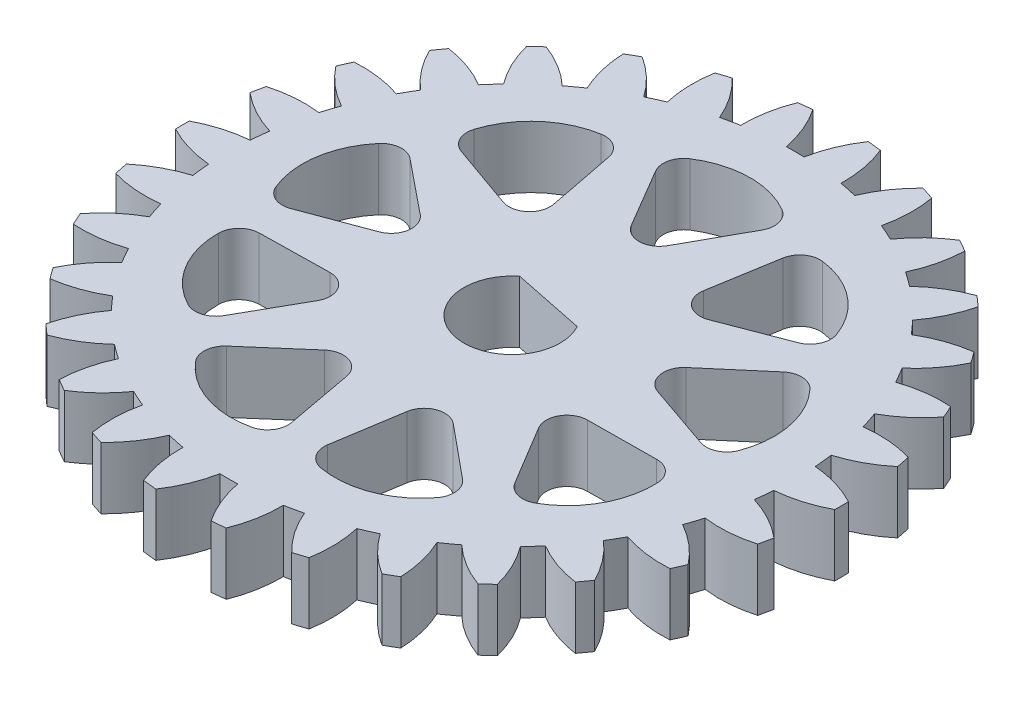
SolidWorks part; units mm, degrees
ref_plane "Front Plane" through (0, 0, 0) normal (0, 0, 1) x (1, 0, 0)
ref_plane "Top Plane" through (0, 0, 0) normal (0, 1, 0) x (1, 0, 0)
ref_plane "Right Plane" through (0, 0, 0) normal (1, 0, 0) x (0, 0, -1)
sketch "Sketch1" plane through (0, 0, 0) normal (0, 1, 0) x (1, 0, 0)
  line L0 (0, 0) -> (0, 30.7861) construction
  line L1 (0, 0) -> (-3.3399, 31.7772) construction
  line L2 (-1.5563, 14.807) -> (-0.7752, 14.8891) construction
  circle A0 centre (0, 0) radius 16
  circle A1 centre (0, 0) radius 13.75 construction
  circle A2 centre (0, 0) radius 14.0954 construction
  circle A3 centre (0, 0) radius 15 construction
  arc A4 (-1.3398, 15.9438) -> (-0.431, 13.7432) centre (-6.3208, 12.5987) cw
  arc A5 (0.431, 13.7432) -> (1.3398, 15.9438) centre (6.3208, 12.5987) cw
  arc A6 (0.431, 13.7432) -> (-0.431, 13.7432) centre (0, 0) ccw
  dimension "addendumDiameter" = 32
  dimension "D1" = 27.5
  dimension "D2" = 28.1908
  dimension "D3" = 30
  dimension "D5" = 6
  dimension "D4" = 6
  dimension "D6" = 0.7854
extrude "Boss-Extrude1" add sketch "Sketch1" along normal blind 3 contours A5 A6 A4 A0 | A6 A5 A0 A4 region at (0, 0, 0.0681) region at (0, 0, -15.0769)
extrude "Cut-Extrude1" cut sketch "Sketch1<3>" along normal through all contours A6 A5 A0 A4 region at (0, 0, -15.0769)
sketch "Sketch1<3>" plane through (0, 0, 0) normal (0, 1, 0) x (1, 0, 0) same geometry as "Sketch1"
pattern_circular "CirPattern1" count 30 over 360 about axis through (0, 3, 0) along (0, -1, 0) of "Cut-Extrude1"
sketch "Sketch2" [suppressed] plane through (0, 0, 0) normal (0, -1, 0) x (1, 0, 0)
  line L0 (16.1415, -4.0765) -> (5.4849, -1.3852)
  line L1 (2.2797, -16.4915) -> (0.7746, -5.6038)
  arc A0 (2.2797, -16.4915) -> (16.1415, -4.0765) centre (0, 0) ccw
  arc A1 (5.4849, -1.3852) -> (0.7746, -5.6038) centre (0, 0) cw
extrude "Cut-Extrude2" [suppressed] cut sketch "Sketch2" against normal through all
fillet "Fillet2" [suppressed] radius 1
pattern_circular "CirPattern2" [suppressed] count 3 over 360 of bodies 105
sketch "Sketch3" [suppressed] plane through (0, 0, 0) normal (0, -1, 0) x (-1, 0, 0)
  line L0 (-1.7523, 1.5) -> (1.7523, 1.5)
  arc A0 (-1.7523, 1.5) -> (1.7523, 1.5) centre (0, 0) ccw
  dimension "D1" = 1.5
extrude "Cut-Extrude3" [suppressed] cut sketch "Sketch3" against normal through all
sketch "Sketch4" [suppressed] plane through (0, 0, 0) normal (0, -1, 0) x (-1, 0, 0)
  line L0 (-1.9585, 1.1467) -> (1.3849, 1.798)
  arc A0 (-1.9585, 1.1467) -> (1.3849, 1.798) centre (0, 0) ccw
  dimension "D1" = 1.5
extrude "Cut-Extrude4" [suppressed] cut sketch "Sketch4" against normal through all
sketch "Sketch5" [suppressed] plane through (0, 0, 0) normal (0, -1, 0) x (-1, 0, 0)
  line L0 (-1.8915, 1.4085) -> (1.7436, 1.5879)
  arc A0 (-1.8915, 1.4085) -> (1.7436, 1.5879) centre (0, 0) ccw
  dimension "D1" = 1.5
extrude "Cut-Extrude5" [suppressed] cut sketch "Sketch5" against normal blind 10
sketch "Sketch6" plane through (0, 0, 0) normal (0, -1, 0) x (1, 0, 0)
  line L0 (2.0562, -1.1096) -> (-1.4536, -1.8292)
  arc A0 (2.0562, -1.1096) -> (-1.4536, -1.8292) centre (0, 0) ccw
  dimension "D1" = 1.5
extrude "Cut-Extrude6" cut sketch "Sketch6" against normal blind 10
sketch "Sketch8" plane through (0, 0, 0) normal (0, -1, 0) x (-1, 0, 0)
  line L0 (-2.8977, 10.3975) -> (0, 5.1704)
  line L1 (0, 5.1704) -> (3.0113, 10.2839)
  arc A0 (-2.8977, 10.3975) -> (3.0113, 10.2839) centre (0, 7.3862) cw
extrude "Cut-Extrude7" cut sketch "Sketch8" against normal blind 10
pattern_circular "CirPattern3" count 9 over 360 about axis through (0, 0, 0) along (0, 1, 0) of "Cut-Extrude7"
fillet "Fillet3" radius 1 27 edges at (4.4777, 1.5, 2.5852) (7.5557, 1.5, 7.7082) (10.4118, 1.5, 2.5341) (6.347, 1.5, 8.6338) (0.8332, 1.5, 10.7616) (1.7684, 1.5, 4.8586) (-1.7684, 1.5, 4.8586) (-6.2791, 1.5, 8.7794) (-0.6876, 1.5, 10.6936) (-7.4005, 1.5, 7.7498) (-10.4534, 1.5, 2.6893) (-4.4777, 1.5, 2.5852) (-5.0918, 1.5, -0.8978) (-9.7364, 1.5, -4.6592) (-10.6506, 1.5, 1.1798) (-8.9172, 1.5, -5.9423) (-4.4637, 1.5, -9.8276) (-3.3234, 1.5, -3.9607) (0, 1.5, -5.1704) (3.3234, 1.5, -3.9607) (5.0918, 1.5, -0.8978) (9.6048, 1.5, -4.7513) (10.7428, 1.5, 1.0481) (4.3036, 1.5, -9.8136) (8.9032, 1.5, -6.1024) (2.8977, 1.5, -10.3975) (-3.0113, 1.5, -10.2839)
equation "\"module\"= 1.0"
equation "\"teeth\" = 30"
equation "\"pressureAngle\"= 20deg"
equation "\"gearThickness\"= 3"
equation "\"addendumFactor\"= 1"
equation "\"dedendumFactor\"= 1.25"
equation "\"pitch\"= 1 / \"module\""
equation "\"pitchDiameter\"= \"teeth\" / \"pitch\""
equation "\"addendum\"= \"addendumFactor\" / \"pitch\""
equation "\"dedendum\"= \"dedendumFactor\" / \"pitch\""
equation "\"addendumDiameter@Sketch1\" = \"pitchDiameter\" + 2 * \"addendum\""
equation "\"D1@Sketch1\"=\"pitchDiameter\" - 2 * \"dedendum\""
equation "\"D2@Sketch1\"=\"pitchDiameter\" * cos ( \"pressureAngle\" )"
equation "\"D3@Sketch1\"=\"pitchDiameter\""
equation "\"D4@Sketch1\"=180/\"teeth\""
equation "\"D5@Sketch1\"=\"pitchDiameter\"/5"
equation "\"D1@CirPattern1\"=\"teeth\""
equation "\"D6@Sketch1\"=PI/2/\"pitch\"/2"
